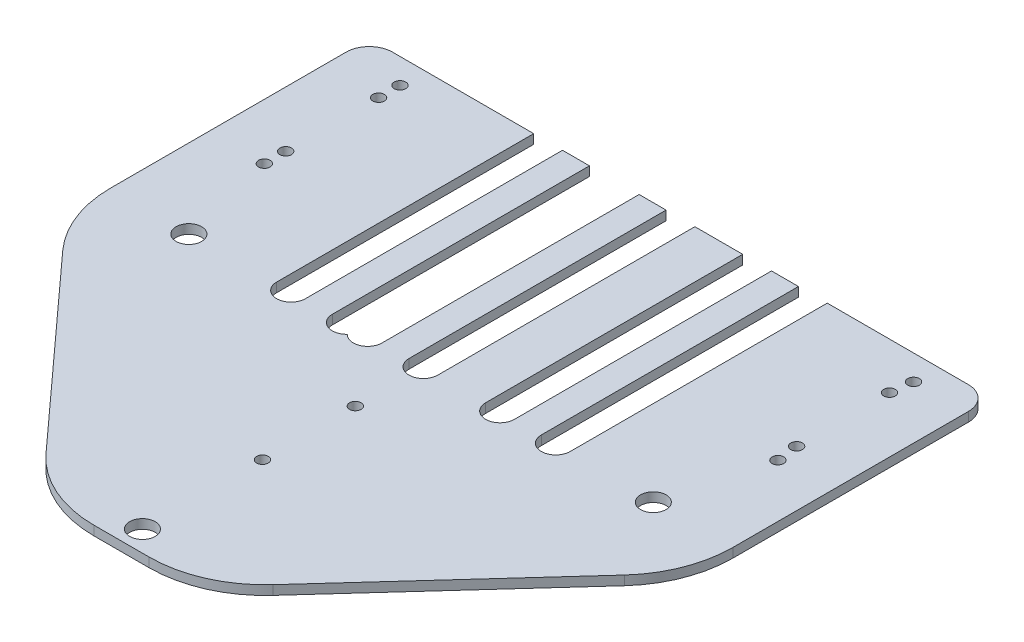
SolidWorks part; units mm, degrees
material "6061 Alloy"
ref_plane "Front Plane" through (0, 0, 0) normal (0, 0, 1) x (1, 0, 0)
ref_plane "Top Plane" through (0, 0, 0) normal (0, 1, 0) x (1, 0, 0)
ref_plane "Right Plane" through (0, 0, 0) normal (1, 0, 0) x (0, 0, -1)
sketch "Sketch1" plane through (0, 0, 0) normal (0, 1, 0) x (1, 0, 0)
  line L1 (0, 0) -> (134, 0)
  line L2 (0, 0) -> (0, 120.35)
  line L3 (0, 120.35) -> (134, 120.35)
  line L4 (134, 0) -> (134, 120.35)
  dimension "D1" = 134
  dimension "D2" = 120.35
extrude "Boss-Extrude1" add sketch "Sketch1" along normal blind 2
sketch "Sketch3" plane through (0, 2, 0) normal (0, 1, 0) x (1, 0, 0)
  line L0 (86.6, 120.35) -> (86.6, 65)
  line L2 (86.6, 120.35) -> (80.4, 120.35)
  line L3 (80.4, 120.35) -> (80.4, 65)
  line L4 (70.1, 120.35) -> (70.1, 65)
  line L5 (70.1, 120.35) -> (63.9, 120.35)
  line L6 (63.9, 120.35) -> (63.9, 65)
  line L7 (98.6, 120.35) -> (98.6, 65)
  line L8 (98.6, 120.35) -> (92.4, 120.35)
  line L9 (92.4, 120.35) -> (92.4, 65)
  line L10 (58.1, 120.35) -> (58.1, 65)
  line L11 (58.1, 120.35) -> (51.9, 120.35)
  line L12 (51.9, 120.35) -> (51.9, 65)
  line L16 (41.6, 120.35) -> (41.6, 65)
  line L17 (41.6, 120.35) -> (35.4, 120.35)
  line L18 (35.4, 120.35) -> (35.4, 65)
  line L19 (134, 120.35) -> (0, 120.35) construction
  line L23 (134, 0) -> (134, 120.35) construction
  arc A0 (80.4, 65) -> (86.6, 65) centre (83.5, 65) ccw
  arc A1 (63.9, 65) -> (70.1, 65) centre (67, 65) ccw
  arc A2 (92.4, 65) -> (98.6, 65) centre (95.5, 65) ccw
  arc A3 (51.9, 65) -> (58.1, 65) centre (55, 65) ccw
  arc A5 (35.4, 65) -> (41.6, 65) centre (38.5, 65) ccw
  dimension "D1" = 3.1
  dimension "D2" = 16.5
  dimension "D4" = 12
  dimension "D5" = 16.5
  dimension "D6" = 12
  dimension "D7" = 55.35
  dimension "D8" = 38.5
extrude "Cut-Extrude1" cut sketch "Sketch3" against normal through all
sketch "Sketch4" plane through (0, 2, 0) normal (0, 1, 0) x (1, 0, 0)
  line L0 (47.4, 120.35) -> (53.6, 120.35)
  line L1 (51.9, 120.35) -> (41.6, 120.35) construction
  line L2 (53.6, 120.35) -> (53.6, 65)
  line L3 (47.4, 120.35) -> (47.4, 65)
  line L4 (41.6, 65) -> (41.6, 120.35) construction
  arc A0 (47.4, 65) -> (53.6, 65) centre (50.5, 65) ccw
  arc A1 (51.9, 65) -> (58.1, 65) centre (55, 65) ccw construction
  dimension "D1" = 4.5
extrude "Cut-Extrude2" cut sketch "Sketch4" against normal through all
hole_wizard "linear bearing" positions "Sketch6" profile "Sketch5" tap size "M3x0.5" standard "ANSI Metric" end condition through all
sketch "Sketch6" plane through (0, 2, 0) normal (0, 1, 0) x (1, 0, 0)
  line L0 (134, 0) -> (134, 120.35) construction
  line L6 (0, 120.35) -> (0, 0) construction
  line L9 (35.4, 120.35) -> (0, 120.35) construction
  point P36 (12, 110.35)
  point P38 (12, 90.35)
  point P40 (122, 110.35)
  point P42 (122, 90.35)
  point P44 (67, 50.35)
  point P46 (67, 30.35)
  dimension "D1" = 67
  dimension "D2" = 12
  dimension "D3" = 10
  dimension "D4" = 12
  dimension "D5" = 20
  dimension "D6" = 40
  dimension "D7" = 20
sketch "Sketch5" plane through (12, 2, -110.35) normal (1, 0, 0) x (0, 0, 1)
  line L0 (0, 0) -> (0, 2)
  line L1 (0, 2) -> (1.25, 2)
  line L2 (1.25, 2) -> (1.25, 0)
  line L5 (1.25, 0) -> (0, 0)
  line L11 (0, -6.35) -> (0, 107.95) construction
  dimension "Thread Major Dia." = 2.5
  dimension "Thru Tap Drill Depth" = 2
hole_wizard "belt holders" positions "Sketch8" profile "Sketch7" tap size "M3x0.5" standard "ANSI Metric" end condition through all
sketch "Sketch8" plane through (0, 2, 0) normal (0, 1, 0) x (1, 0, 0)
  line L0 (0, 120.35) -> (0, 0) construction
  circle A0 centre (12, 110.35) radius 1.25 construction
  circle A1 centre (12, 90.35) radius 1.25 construction
  point P0 (12, 114.95)
  point P2 (12, 85.75)
  point P4 (122.5813, 85.75)
  point P6 (122.5813, 114.95)
  dimension "D2" = 4.6
  dimension "D1" = 12
  dimension "D3" = 4.6
cosmetic thread "Hole Thread1" parameters "D2"=3
cosmetic thread "Hole Thread2" parameters "D2"=3
cosmetic thread "Hole Thread3" parameters "D2"=3
cosmetic thread "Hole Thread4" parameters "D2"=3
sketch "Sketch7" plane through (12, 2, -114.95) normal (1, 0, 0) x (0, 0, 1)
  line L0 (0, 0) -> (0, 2)
  line L1 (0, 2) -> (1.25, 2)
  line L2 (1.25, 2) -> (1.25, 0)
  line L5 (1.25, 0) -> (0, 0)
  line L11 (0, -6.35) -> (0, 107.95) construction
  dimension "Thru Tap Drill Dia." = 2.5
  dimension "Thru Tap Drill Depth" = 2
sketch "Sketch9" plane through (0, 2, 0) normal (0, 1, 0) x (1, 0, 0)
  line L0 (0, 55) -> (50, 0)
  line L1 (0, 120.35) -> (0, 0) construction
  line L2 (0, 0) -> (134, 0) construction
  line L3 (50, 0) -> (0, 0)
  line L4 (0, 0) -> (0, 55)
  line L5 (134, 0) -> (134, 55)
  line L6 (134, 0) -> (134, 120.35) construction
  line L7 (134, 55) -> (84, 0)
  line L8 (84, 0) -> (134, 0)
  dimension "D1" = 50
  dimension "D2" = 55
extrude "Cut-Extrude3" cut sketch "Sketch9" against normal through all
fillet "Fillet1" radius 5 2 edges at (134, 1, -120.35) (0, 1, -120.35)
fillet "Fillet2" radius 25 4 edges at (134, 1, -55) (84, 1, 0) (50, 1, 0) (0, 1, -55)
hole_wizard "Ø5.5 (5.5) Diameter Hole1" positions "Sketch11" profile "Sketch10" hole size "Ø5.5" standard "ANSI Metric" end condition through all
sketch "Sketch11" plane through (0, 2, 0) normal (0, 1, 0) x (1, 0, 0)
  line L0 (134, 64.6652) -> (134, 115.35) construction
  line L1 (61.0592, 0) -> (72.9408, 0) construction
  point P0 (67, 4.5)
  point P2 (117, 64.5)
  point P4 (17, 64.5)
  dimension "D1" = 67
  dimension "D2" = 50
  dimension "D3" = 50
  dimension "D4" = 60
  dimension "D5" = 4.5
sketch "Sketch10" plane through (67, 2, -4.5) normal (1, 0, 0) x (0, 0, 1)
  line L0 (0, 0) -> (0, 2)
  line L1 (0, 2) -> (2.75, 2)
  line L2 (2.75, 2) -> (2.75, 0)
  line L5 (2.75, 0) -> (0, 0)
  line L11 (0, -6.35) -> (0, 107.95) construction
  dimension "Thru Hole Dia." = 5.5
  dimension "Thru Hole Depth" = 2
